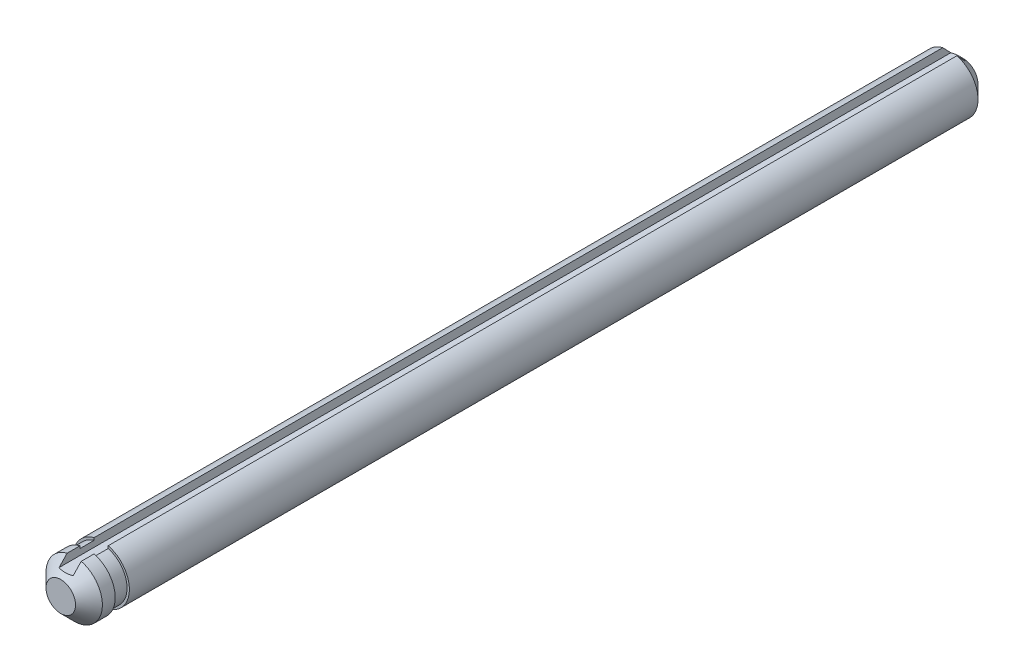
SolidWorks part; units mm, degrees
ref_plane "Front Plane" through (0, 0, 0) normal (0, 0, 1) x (1, 0, 0)
ref_plane "Top Plane" through (0, 0, 0) normal (0, 1, 0) x (1, 0, 0)
ref_plane "Right Plane" through (0, 0, 0) normal (1, 0, 0) x (0, 0, -1)
sketch "Sketch1" plane through (0, 0, 0) normal (1, 0, 0) x (0, 0, -1)
  line L0 (0, 0) -> (0, 4) construction
  line L1 (-250, 4) -> (250, 4)
  line L2 (-250, 4) -> (-250, -4)
  line L3 (-250, -4) -> (250, -4)
  line L4 (250, 4) -> (250, -4)
  line L5 (-250, 4) -> (250, -4) construction
  line L6 (-250, -4) -> (250, 4) construction
  line L7 (0, 0) -> (0, -4) construction
  point P0 (0, 0)
  point P8 (-240.8, 4)
  point P10 (240.8, 4)
  dimension "Diameter" = 8
  dimension "Length" = 500
  dimension "D1" = 9.2
  dimension "D2" = 9.2
sketch "Sketch2" plane through (0, 0, 0) normal (0, 0, 1) x (1, 0, 0)
  line L0 (0, 0) -> (0, 4) construction
  line L2 (1, 2.673) -> (-1, 2.673)
  line L3 (1, 2.673) -> (1, 3.873)
  line L4 (1, 3.873) -> (-1, 3.873)
  line L5 (-1, 2.673) -> (-1, 3.873)
  line L6 (1, 2.673) -> (-1, 3.873) construction
  line L7 (1, 3.873) -> (-1, 2.673) construction
  circle A0 centre (0, 0) radius 4
  point P3 (0, 3.273)
  dimension "Keyway Width" = 2
  dimension "Keyway Depth" = 1.2
sketch "Sketch3" plane through (0, 0, 0) normal (0, 0, 1) x (1, 0, 0)
  line L1 (-1, 2.673) -> (-1, 3.873) construction
  line L2 (1, 2.673) -> (-1, 2.673) construction
  line L3 (1, 2.673) -> (1, 3.873) construction
  line L5 (-1, 2.673) -> (-1, 3.873)
  line L6 (1, 2.673) -> (-1, 2.673)
  line L7 (1, 2.673) -> (1, 3.873)
  circle A0 centre (0, 0) radius 4 construction
  arc A1 (-1, 3.873) -> (1, 3.873) centre (0, 0) ccw
extrude "Boss-Extrude1" add sketch "Sketch3" along normal mid plane 128
chamfer "Chamfer1" distance 1.905 angle 45 2 edges at (0, -4, 64) (0, -4, -64)
ref_axis "Axis1" through (0, 0, 62.095) along (0, 0, -1)
sketch "Sketch4" plane through (0, 0, 0) normal (1, 0, 0) x (0, 0, -1)
  line L0 (-62.095, 3.873) -> (62.095, 3.873) construction
  line L1 (-58.2684, 4.8373) -> (-60.275, 4.8373)
  line L2 (-58.2684, 4.8373) -> (-58.2684, 3.673)
  line L3 (-58.2684, 3.673) -> (-60.275, 3.673)
  line L4 (-60.275, 4.8373) -> (-60.275, 3.673)
  line L6 (-59.375, 1.2319) -> (-59.375, -7.2413) construction
  dimension "D1" = 0.2
  dimension "D2" = 0.9
  dimension "D3" = 2.0066
revolve "Cut-Revolve1" cut sketch "Sketch4" angle 360 about axis through (0, 0, 62.095) along (0, 0, -1)
equation "\"D2@Sketch1\"=1.15*\"Diameter@Sketch1\""
equation "\"D1@Sketch1\"=\"D2@Sketch1\""
